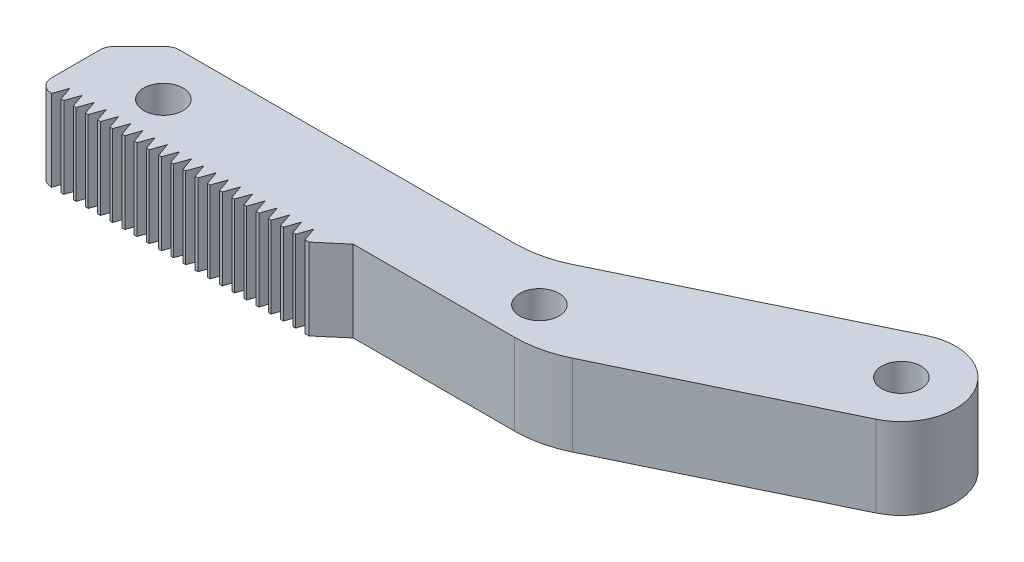
SolidWorks part; units mm, degrees
ref_plane "Alzado" through (0, 0, 0) normal (0, 0, 1) x (1, 0, 0)
ref_plane "Planta" through (0, 0, 0) normal (0, 1, 0) x (1, 0, 0)
ref_plane "Vista lateral" through (0, 0, 0) normal (1, 0, 0) x (0, 0, -1)
sketch "Croquis base" plane through (0, 0, 0) normal (0, 1, 0) x (1, 0, 0)
  line L0 (0, 0) -> (-32.5, 0) construction
  line L1 (-32.5, 0) -> (-32.5, -0.903) construction
  line L2 (0, 0) -> (-32.5, -0.903) construction
  line L4 (0, 0) -> (21.6055, 0) construction
  line L7 (2.9841, -3) -> (-10.738, -3)
  line L9 (-2.9841, 3) -> (-30, 3)
  line L10 (-32.5, -3) -> (-32.5, 0.5)
  line L11 (0, 0) -> (21.6055, 10.45) construction
  line L12 (21.6055, 10.45) -> (21.6055, 0) construction
  line L14 (-2.9841, 3) -> (16.2629, 12.3092)
  line L16 (2.9841, -3) -> (19.7462, 5.1074)
  line L21 (-32.5, -3) -> (-32.5, -4.5)
  line L22 (-32.5, -4.5) -> (-12.5, -4.5) construction
  line L24 (-31.15, -3.5) -> (-13.15, -3.5) construction
  line L25 (-32.5, -4.5) -> (-31.5, -4.5)
  line L26 (-32.5, -4.5) -> (-32.5, -3.5)
  line L27 (-31.15, -4.5) -> (-31.15, -3.5) construction
  line L29 (-31.5, -4.5) -> (-31.15, -3.5)
  line L30 (-31.15, -3.5) -> (-30.8, -4.5)
  line L31 (-30.8, -4.5) -> (-30.6, -4.5)
  line L32 (-30.6, -4.5) -> (-30.25, -3.5)
  line L33 (-30.25, -3.5) -> (-29.9, -4.5)
  line L34 (-29.9, -4.5) -> (-29.7, -4.5)
  line L35 (-29.7, -4.5) -> (-29.35, -3.5)
  line L36 (-29.35, -3.5) -> (-29, -4.5)
  line L37 (-29, -4.5) -> (-28.8, -4.5)
  line L38 (-28.8, -4.5) -> (-28.45, -3.5)
  line L39 (-28.45, -3.5) -> (-28.1, -4.5)
  line L40 (-28.1, -4.5) -> (-27.9, -4.5)
  line L41 (-27.9, -4.5) -> (-27.55, -3.5)
  line L42 (-27.55, -3.5) -> (-27.2, -4.5)
  line L43 (-27.2, -4.5) -> (-27, -4.5)
  line L44 (-27, -4.5) -> (-26.65, -3.5)
  line L45 (-26.65, -3.5) -> (-26.3, -4.5)
  line L46 (-26.3, -4.5) -> (-26.1, -4.5)
  line L47 (-26.1, -4.5) -> (-25.75, -3.5)
  line L48 (-25.75, -3.5) -> (-25.4, -4.5)
  line L49 (-25.4, -4.5) -> (-25.2, -4.5)
  line L50 (-25.2, -4.5) -> (-24.85, -3.5)
  line L51 (-24.85, -3.5) -> (-24.5, -4.5)
  line L52 (-24.5, -4.5) -> (-24.3, -4.5)
  line L53 (-24.3, -4.5) -> (-23.95, -3.5)
  line L54 (-23.95, -3.5) -> (-23.6, -4.5)
  line L55 (-23.6, -4.5) -> (-23.4, -4.5)
  line L56 (-23.4, -4.5) -> (-23.05, -3.5)
  line L57 (-23.05, -3.5) -> (-22.7, -4.5)
  line L58 (-22.7, -4.5) -> (-22.5, -4.5)
  line L59 (-22.5, -4.5) -> (-22.15, -3.5)
  line L60 (-22.15, -3.5) -> (-21.8, -4.5)
  line L61 (-21.8, -4.5) -> (-21.6, -4.5)
  line L62 (-21.6, -4.5) -> (-21.25, -3.5)
  line L63 (-21.25, -3.5) -> (-20.9, -4.5)
  line L64 (-20.9, -4.5) -> (-20.7, -4.5)
  line L65 (-20.7, -4.5) -> (-20.35, -3.5)
  line L66 (-20.35, -3.5) -> (-20, -4.5)
  line L67 (-20, -4.5) -> (-19.8, -4.5)
  line L68 (-19.8, -4.5) -> (-19.45, -3.5)
  line L69 (-19.45, -3.5) -> (-19.1, -4.5)
  line L70 (-19.1, -4.5) -> (-18.9, -4.5)
  line L71 (-18.9, -4.5) -> (-18.55, -3.5)
  line L72 (-18.55, -3.5) -> (-18.2, -4.5)
  line L73 (-18.2, -4.5) -> (-18, -4.5)
  line L74 (-18, -4.5) -> (-17.65, -3.5)
  line L75 (-17.65, -3.5) -> (-17.3, -4.5)
  line L76 (-17.3, -4.5) -> (-17.1, -4.5)
  line L77 (-17.1, -4.5) -> (-16.75, -3.5)
  line L78 (-16.75, -3.5) -> (-16.4, -4.5)
  line L79 (-16.4, -4.5) -> (-16.2, -4.5)
  line L80 (-16.2, -4.5) -> (-15.85, -3.5)
  line L81 (-15.85, -3.5) -> (-15.5, -4.5)
  line L82 (-15.5, -4.5) -> (-15.3, -4.5)
  line L83 (-15.3, -4.5) -> (-14.95, -3.5)
  line L84 (-14.95, -3.5) -> (-14.6, -4.5)
  line L85 (-14.6, -4.5) -> (-14.4, -4.5)
  line L86 (-14.4, -4.5) -> (-14.05, -3.5)
  line L87 (-14.05, -3.5) -> (-13.7, -4.5)
  line L88 (-13.7, -4.5) -> (-13.5, -4.5)
  line L89 (-13.5, -4.5) -> (-13.15, -3.5)
  line L90 (-13.15, -3.5) -> (-12.8, -4.5)
  line L91 (-12.8, -4.5) -> (-12.6, -4.5)
  line L92 (-12.6, -4.5) -> (-12.5, -4.5)
  line L93 (-12.5, -4.5) -> (-10.738, -3)
  line L94 (-32.5, 0.5) -> (-30, 3)
  line L95 (-32.5, 3) -> (-30, 3) construction
  line L97 (-32.5, 0.5) -> (-30, 0.5) construction
  line L98 (-30, 3) -> (-30, 0.5) construction
  arc A4 (19.7462, 5.1074) -> (16.2629, 12.3092) centre (18.0046, 8.7083) ccw
  circle A5 centre (-27, -0.7502) radius 1.45
  circle A6 centre (0, 0) radius 1.45
  circle A7 centre (18.0046, 8.7083) radius 1.45
  dimension "D13" = 1
  dimension "D8" = 8
  dimension "D22" = 2.9
  dimension "D1" = 32.5
  dimension "D2" = 0.903
  dimension "D3" = 6
  dimension "D4" = 3
  dimension "D5" = 25.812
  dimension "D6" = 24
  dimension "D7" = 10.45
  dimension "D9" = 4
  dimension "D10" = 4
  dimension "D11" = 20
  dimension "D12" = 1.5
  dimension "D14" = 1
  dimension "D15" = 0.35
  dimension "D16" = 0.35
  dimension "D17" = 0.2
  dimension "D18" = 5.5
  dimension "D19" = 1.592
  dimension "D21" = 2.5
  dimension "D20" = 2.5
extrude "Saliente-Extruir1" add sketch "Croquis base" along normal blind 6 contours L16 A4 L14 L9 L94 L10 L21 L25 L29 L30 L31 L32 L33 L34 L35 L36 L37 L38 L39 L40 L41 L42 L43 L44 L45 L46 L47 L48 L49 L50 L51 L52 L53 L54 L55 L56 L57 L58 L59 L60 L61 L62 L63 L64 L65 L66 L67 L68 L69 L70 region at (-4.2156, 0, -2.053)
fillet "Redondeo1" radius 1 3 edges at (-30, 3, -3) (-32.5, 3, -0.5) (-32.5, 3, 4.5)
fillet "Redondeo2" radius 8 2 edges at (-2.9841, 3, -3) (2.9841, 3, 3)
